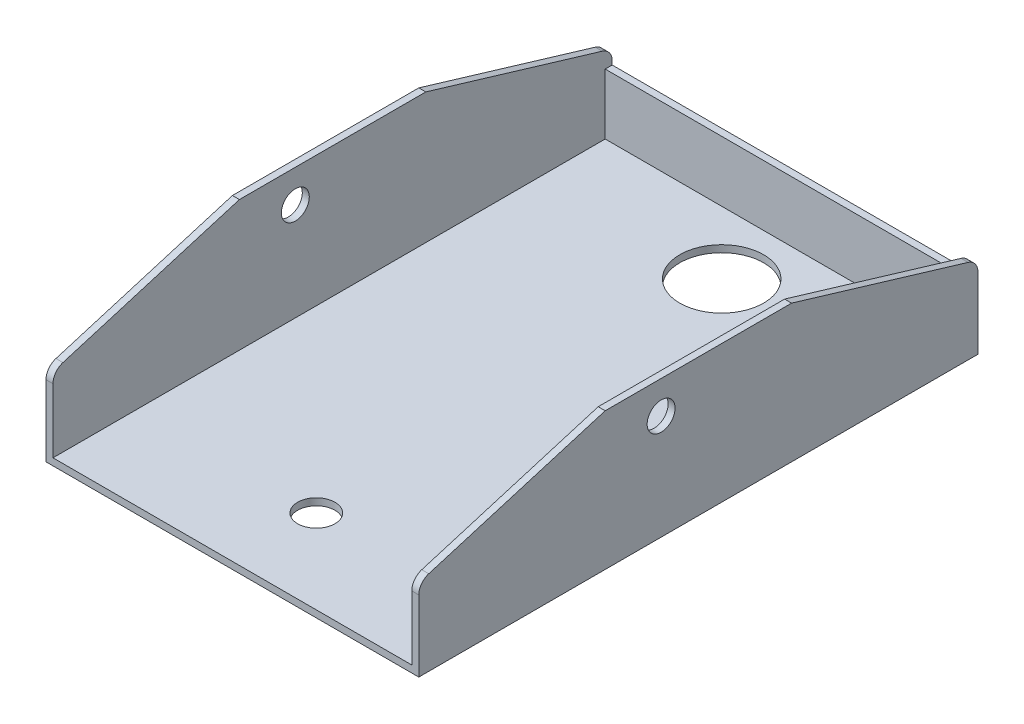
SolidWorks part; units mm, degrees
ref_plane "Front Plane" through (0, 0, 0) normal (0, 0, 1) x (1, 0, 0)
ref_plane "Top Plane" through (0, 0, 0) normal (0, 1, 0) x (1, 0, 0)
ref_plane "Right Plane" through (0, 0, 0) normal (1, 0, 0) x (0, 0, -1)
sketch "Sketch1" plane through (0, 0, 0) normal (0, 1, 0) x (1, 0, 0)
  line L1 (-40, -60) -> (40, -60)
  line L2 (-40, -60) -> (-40, 60)
  line L3 (-40, 60) -> (40, 60)
  line L4 (40, -60) -> (40, 60)
  line L5 (-40, -60) -> (40, 60) construction
  line L6 (-40, 60) -> (40, -60) construction
  circle A0 centre (0, -42) radius 4
  circle A1 centre (0, 45) radius 9
  point P0 (0, 0)
  dimension "D3" = 18
  dimension "D4" = 8
  dimension "D5" = 15
  dimension "D6" = 18
  dimension "D1" = 120
  dimension "D2" = 80
extrude "Boss-Extrude1" add sketch "Sketch1" along normal blind 1.5
sketch "Sketch2" plane through (0, 1.5, 0) normal (0, 1, 0) x (1, 0, 0)
  line L0 (-40, -60) -> (40, -60) construction
  line L2 (-40, 58.5) -> (-40, -60)
  line L3 (-40, -60) -> (-38.5, -60)
  line L4 (-38.5, 60) -> (-38.5, -60)
  line L5 (-38.5, 60) -> (-40, 60)
  line L7 (40, 60) -> (40, -60)
  line L8 (40, -60) -> (38.5, -60)
  line L9 (38.5, 60) -> (38.5, -60)
  line L10 (-38.5, 60) -> (38.5, 60)
  line L12 (-38.5, 58.5) -> (38.5, 58.5)
  line L13 (40, 60) -> (40, 58.5)
  line L14 (-40, 60) -> (-40, 58.5)
  line M13 (40, -60) -> (40, 60)
  line M14 (40, 60) -> (-40, 60)
  line M15 (-40, 60) -> (-40, -60)
  line M16 (-40, -60) -> (40, -60)
  dimension "D1" = 1.5
  dimension "D2" = 1.5
  dimension "D3" = 1.5
extrude "Boss-Extrude2" add sketch "Sketch2" along normal blind 28 contours L4 M14 M15 M16 | L9 L7 M14 M16 M13 region at (-39.25, 1.5, 0) region at (39.25, 1.5, 0)
extrude "Boss-Extrude3" add sketch "Sketch2<3>" along normal blind 13 contours L4 L12 L9 M14 region at (0, 1.5, -59.25)
sketch "Sketch2<3>" plane through (0, 1.5, 0) normal (0, 1, 0) x (1, 0, 0) same geometry as "Sketch2"
sketch "Sketch3" plane through (0, 0, 0) normal (1, 0, 0) x (0, 0, -1)
  line L0 (20, 29.5) -> (60, 29.5)
  line L1 (-60, 29.5) -> (60, 29.5) construction
  line L2 (60, 29.5) -> (60, 17.5)
  line L3 (60, 29.5) -> (60, 0) construction
  line L4 (60, 17.5) -> (20, 29.5)
  line L5 (0, 0) -> (0, 10.1431) construction
  line L6 (-60, 17.5) -> (-20, 29.5)
  line L7 (-60, 29.5) -> (-60, 17.5)
  line L8 (-20, 29.5) -> (-60, 29.5)
  line L9 (-60, 29.5) -> (-60, 0) construction
  circle A0 centre (-8, 22.5) radius 3
  dimension "D3" = 7
  dimension "D4" = 52
  dimension "D5" = 6
  dimension "D1" = 40
  dimension "D2" = 12
extrude "Cut-Extrude1" cut sketch "Sketch3" against normal through all both and the other way through all
fillet "Fillet1" radius 3 4 edges at (39.25, 17.5, 60) (-39.25, 17.5, 60) (-39.25, 17.5, -60) (39.25, 17.5, -60)
